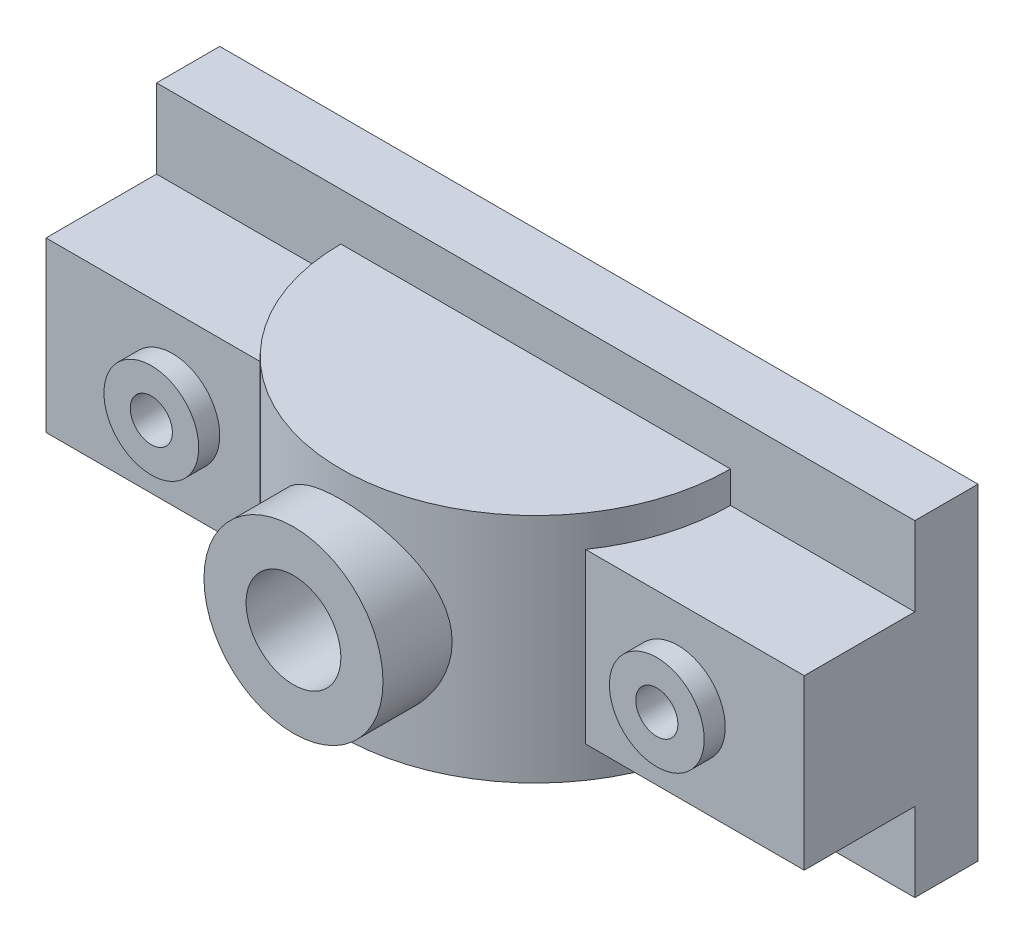
SolidWorks part; units mm, degrees
material "1060 Alloy"
ref_plane "Front Plane" through (0, 0, 0) normal (1, 0, 0) x (0, 1, 0)
ref_plane "Top Plane" through (0, 0, 0) normal (0, 0, 1) x (0, 1, 0)
ref_plane "Right Plane" through (0, 0, 0) normal (0, 1, 0) x (-1, 0, 0)
sketch "Sketch1" plane through (0, 0, 0) normal (0, 0, 1) x (0, 1, 0)
  line L0 (-69.1706, 0) -> (112.3868, 0) construction
  line L1 (-31, 72) -> (31, 72)
  line L2 (-31, 72) -> (-31, -72)
  line L3 (-31, -72) -> (31, -72)
  line L4 (31, 72) -> (31, -72)
  line L5 (-22, -37) -> (-22, 37)
  line L6 (-22, 37) -> (22, 37)
  line L7 (22, 37) -> (22, -37)
  line L8 (22, 0) -> (13, 0)
  line L9 (13, -25) -> (13, 25)
  line L10 (13, 25) -> (-13, 25)
  line L11 (-13, 25) -> (-13, -25)
  line L12 (-13, 0) -> (-22, 0)
  line L13 (13, -25) -> (-13, -25)
  line L14 (-22, -37) -> (22, -37)
  line L15 (-9, 65) -> (-9, -65)
  line L16 (-9, -65) -> (9, -65)
  line L17 (9, -65) -> (9, 65)
  line L18 (9, 65) -> (-9, 65)
  circle A0 centre (0, 48) radius 9
  circle A1 centre (0, 48) radius 4
  circle A2 centre (0, -48) radius 4
  circle A3 centre (0, -48) radius 9
  circle A4 centre (0, 0) radius 17
  circle A5 centre (0, 0) radius 9
  point P4 (0, 72)
  point P6 (31, 0)
  point P11 (0, 37)
  point P18 (0, 25)
  point P25 (0, -65)
  dimension "D10" = 18
  dimension "D11" = 8
  dimension "D12" = 48
  dimension "D13" = 34
  dimension "D14" = 18
  dimension "D1" = 144
  dimension "D2" = 62
  dimension "D3" = 44
  dimension "D4" = 26
  dimension "D5" = 12
  dimension "D6" = 25
  dimension "D7" = 18
  dimension "D8" = 65
  dimension "D9" = 130
extrude "Boss-Extrude1" add sketch "Sketch1" against normal blind 12 contours L0 L2 L3 L4 L7 L14 L17 L16 L15 L5 | L2 L0 L5 L6 L15 L18 L17 L7 L4 L1 | A4 L8 L7 L6 L17 L10 L9 | A4 L11 L10 L15 L6 L5 L12 | A4 L12 L5 L14 L15 L13 L11 | A4 L9 L13 L17 L14 L7 L8 | L12 A4 L11 | L11 A4 L12 | L8 A4 L9 | L9 A4 L8 region at (-4.181, 14.6173, 0) region at (4.181, 14.6173, 0) region at (-21.4321, 16.8573, 0) region at (21.4321, 16.8573, 0) region at (4.181, -14.6173, 0) region at (-4.181, -14.6173, 0) region at (-18.5, 22.9502, 0) region at (0.9502, 26.5, 0) region at (21.4321, -16.8573, 0) region at (-21.4321, -16.8573, 0)
revolve "Revolve1" add sketch "Sketch1<3>" angle 180 about L0 region at (21.4321, -16.8573, 0) region at (31, 0, 0) region at (21.4321, 16.8573, 0) reverse direction yes
sketch "Sketch1<3>" plane through (0, 0, 0) normal (0, 0, 1) x (0, 1, 0) same geometry as "Sketch1"
extrude "Boss-Extrude2" add sketch "Sketch1<4>" along normal blind 21 from offset 25 contours A5 L15 A4 L17 | L0 L11 A4 L15 | L11 L0 L15 A4 | L0 L17 A4 L9 | L9 A4 L8 | L8 A4 L9 | L12 A4 L11 | L11 A4 L12 | A5 L17 A4 L15 | L17 L0 L9 A4 region at (-6.4743, 10.911, 0) region at (6.4743, 10.911, 0) region at (-11.4285, 0, 0) region at (11.4285, 0, 0) region at (-4.181, 14.6173, 0) region at (4.181, 14.6173, 0) region at (6.4743, -10.911, 0) region at (-6.4743, -10.911, 0) region at (4.181, -14.6173, 0) region at (-4.181, -14.6173, 0)
sketch "Sketch1<4>" plane through (0, 0, 0) normal (0, 0, 1) x (0, 1, 0) same geometry as "Sketch1"
sketch "Sketch2" plane through (0, 0, 0) normal (0, 1, 0) x (-1, 0, 0)
  line L0 (-30.4631, 0) -> (-30.4631, 21)
  line L1 (72, 0) -> (-72, 0) construction
  line L2 (-30.4631, 21) -> (-72, 21)
  line L3 (-72, 21) -> (-72, 0)
  line L4 (-72, 0) -> (-30.4631, 0)
  line L5 (30.4631, 0) -> (30.4631, 21)
  line L6 (30.4631, 21) -> (72, 21)
  line L7 (72, 21) -> (72, 0)
  line L8 (72, 0) -> (30.4631, 0)
  line L9 (25, 0) -> (25, 13)
  line L10 (25, 13) -> (65, 13)
  line L11 (65, 13) -> (65, 0)
  line L12 (65, 0) -> (25, 0)
  line L13 (-25, 0) -> (-25, 13)
  line L14 (-25, 13) -> (-65, 13)
  line L15 (-65, 13) -> (-65, 0)
  line L16 (-65, 0) -> (-25, 0)
  arc A0 (37, 0) -> (-37, 0) centre (0, 0) ccw construction
  dimension "D1" = 21
  dimension "D2" = 13
extrude "Boss-Extrude3" add sketch "Sketch2" along normal mid plane 32 contours L15 L14 L0 L2 L3 L4 | L14 L15 L4 L0 | L11 L10 L5 L8 | L10 L11 L8 L7 L6 L5 region at (47.7315, 0, 6.5) region at (54.9439, 0, 14.7427) region at (-47.7315, 0, 6.5) region at (-54.9439, 0, 14.7427)
sketch "Sketch3" plane through (0, 0, 0) normal (1, 0, 0) x (0, 1, 0)
  line L1 (-9, 0) -> (9, 0)
  line L2 (-9, 0) -> (-9, 13)
  line L3 (-9, 13) -> (9, 13)
  line L4 (9, 0) -> (9, 13)
  dimension "D1" = 18
  dimension "D2" = 13
extrude "Cut-Extrude2" cut sketch "Sketch3" against normal mid plane 130
extrude "Boss-Extrude4" add sketch "Sketch1<5>" along normal blind 4 from offset 21 contours A0 A1 | A3 A2 region at (39.2546, 0, 0) region at (-56.7454, 0, 0)
sketch "Sketch1<5>" plane through (0, 0, 0) normal (0, 0, 1) x (0, 1, 0) same geometry as "Sketch1"
extrude "Cut-Extrude3" cut sketch "Sketch1<6>" against normal through all both and the other way through all contours A2 | L0 A5 | A5 L0 | A1 region at (3.8197, 0, 0) region at (-3.8197, 0, 0) region at (-48, 0, 0) region at (48, 0, 0)
sketch "Sketch1<6>" plane through (0, 0, 0) normal (0, 0, 1) x (0, 1, 0) same geometry as "Sketch1"
